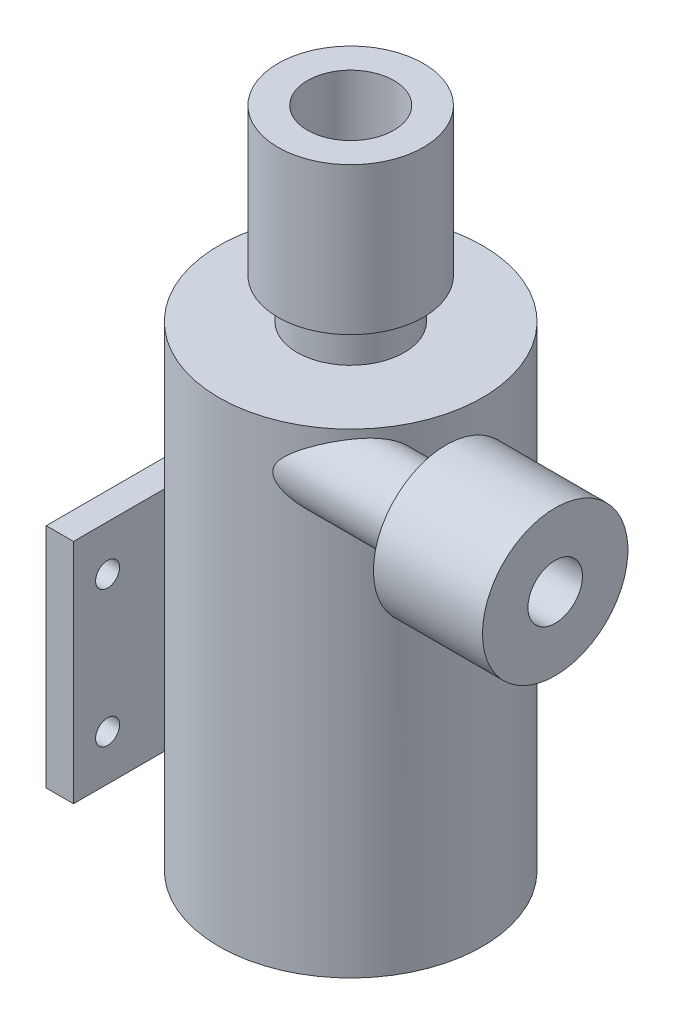
SolidWorks part; units mm, degrees
material "Delrin 2700 NC010, Low Viscosity Acetal Copolymer (SS)"
ref_plane "Front" through (0, 0, 0) normal (0, 0, 1) x (1, 0, 0)
ref_plane "Top" through (0, 0, 0) normal (0, 1, 0) x (1, 0, 0)
ref_plane "Right" through (0, 0, 0) normal (1, 0, 0) x (0, 0, -1)
sketch "Sketch1" plane through (0, 0, 0) normal (0, 1, 0) x (1, 0, 0)
  circle A0 centre (0, 0) radius 18.415
  dimension "D1" = 36.83
extrude "Boss-Extrude1" add sketch "Sketch1" along normal blind 66.421
sketch "Sketch2" plane through (0, 66.421, 0) normal (0, 1, 0) x (1, 0, 0)
  circle A0 centre (0, 0) radius 7.493
  dimension "D1" = 14.986
extrude "Boss-Extrude2" add sketch "Sketch2" along normal blind 5.588
sketch "Sketch3" plane through (0, 72.009, 0) normal (0, 1, 0) x (1, 0, 0)
  circle A0 centre (0, 0) radius 10.16
  circle A1 centre (0, 0) radius 6.0325
  dimension "D1" = 20.32
  dimension "D2" = 12.065
extrude "Boss-Extrude3" add sketch "Sketch3" along normal blind 20.574
sketch "Sketch4" plane through (0, 0, 0) normal (1, 0, 0) x (0, 0, -1)
  line L0 (18.415, 66.421) -> (-18.415, 66.421) construction
  line L1 (-18.415, 66.421) -> (-18.415, 0) construction
  circle A0 centre (-12.065, 60.071) radius 5.207
  dimension "D1" = 10.414
  dimension "D2" = 6.35
  dimension "D3" = 6.35
extrude "Boss-Extrude4" add sketch "Sketch4" along normal blind 25.4
sketch "Sketch5" plane through (25.4, 0, 0) normal (1, 0, 0) x (0, 0, -1)
  circle A0 centre (-12.065, 60.071) radius 10.16
  circle A1 centre (-12.065, 60.071) radius 3.81
  dimension "D1" = 20.32
  dimension "D2" = 7.62
extrude "Boss-Extrude5" add sketch "Sketch5" along normal blind 15.24
sketch "Sketch6" plane through (0, 0, 0) normal (1, 0, 0) x (0, 0, -1)
  line L0 (0, 0) -> (0, 26.797) construction
  line L1 (-18.415, 0) -> (18.415, 0) construction
  line L2 (-22.225, 42.672) -> (22.225, 42.672)
  line L3 (-22.225, 42.672) -> (-22.225, 10.922)
  line L4 (-22.225, 10.922) -> (22.225, 10.922)
  line L5 (22.225, 42.672) -> (22.225, 10.922)
  line L6 (-22.225, 42.672) -> (22.225, 10.922) construction
  line L7 (-22.225, 10.922) -> (22.225, 42.672) construction
  line L9 (-17.4625, 36.322) -> (17.4625, 36.322) construction
  line L10 (-17.4625, 36.322) -> (-17.4625, 17.272) construction
  line L11 (-17.4625, 17.272) -> (17.4625, 17.272) construction
  line L12 (17.4625, 36.322) -> (17.4625, 17.272) construction
  line L13 (-17.4625, 36.322) -> (17.4625, 17.272) construction
  line L14 (-17.4625, 17.272) -> (17.4625, 36.322) construction
  circle A0 centre (-17.4625, 36.322) radius 1.6764
  circle A1 centre (17.4625, 36.322) radius 1.6764
  circle A2 centre (17.4625, 17.272) radius 1.6764
  circle A3 centre (-17.4625, 17.272) radius 1.6764
  dimension "D4" = 3.3528
  dimension "D1" = 44.45
  dimension "D2" = 31.75
  dimension "D3" = 10.922
  dimension "D5" = 34.925
  dimension "D6" = 19.05
extrude "Boss-Extrude6" add sketch "Sketch6" along normal blind 3.81 from offset 20.32 offset against normal yes
